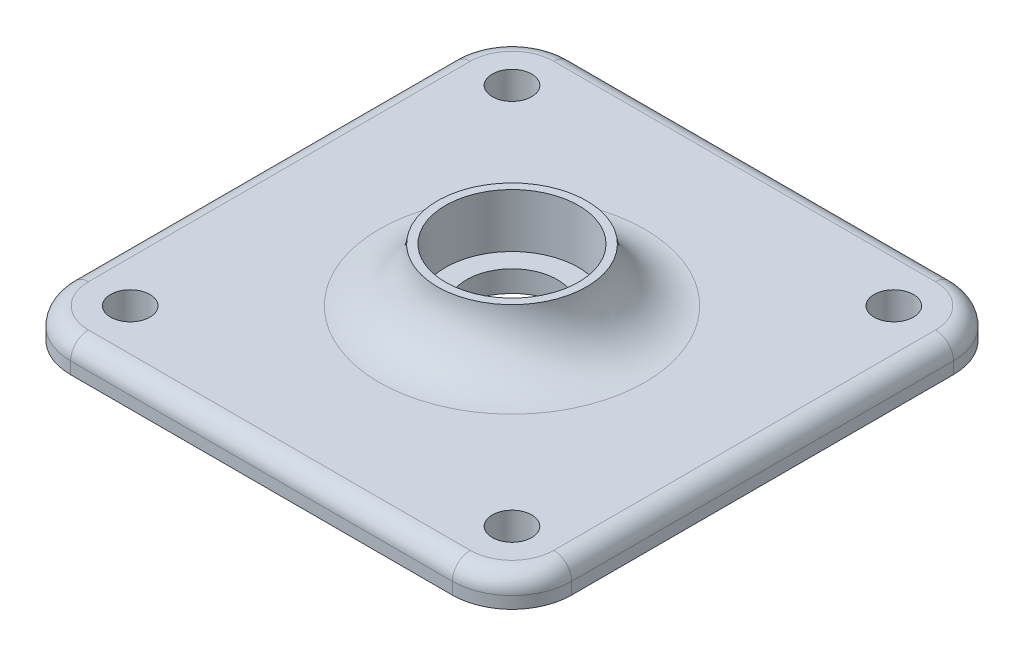
SolidWorks part; units mm, degrees
ref_plane "Front Plane" through (0, 0, 0) normal (0, 0, 1) x (1, 0, 0)
ref_plane "Top Plane" through (0, 0, 0) normal (0, 1, 0) x (1, 0, 0)
ref_plane "Right Plane" through (0, 0, 0) normal (1, 0, 0) x (0, 0, -1)
sketch "Sketch1" plane through (0, 0, 0) normal (0, 1, 0) x (1, 0, 0)
  line L1 (32, 42) -> (-32, 42)
  line L2 (42, 32) -> (42, -32)
  line L3 (32, -42) -> (-32, -42)
  line L4 (-42, 32) -> (-42, -32)
  line L5 (42, 42) -> (-42, -42) construction
  line L6 (42, -42) -> (-42, 42) construction
  arc A0 (32, 42) -> (42, 32) centre (32, 32) cw
  arc A1 (42, -32) -> (32, -42) centre (32, -32) cw
  arc A2 (-32, -42) -> (-42, -32) centre (-32, -32) cw
  arc A3 (-32, 42) -> (-42, 32) centre (-32, 32) ccw
  point P0 (0, 0)
  dimension "D1" = 10
  dimension "D2" = 84
extrude "Boss-Extrude1" add sketch "Sketch1" along normal blind 5 contours L1 A3 L4 A2 L3 A1 L2 A0
sketch "Sketch3" plane through (0, 0, 0) normal (0, 0, 1) x (1, 0, 0)
  line L0 (32, 5) -> (-32, 5) construction
  line L1 (0, 5) -> (-12.5, 5) construction
  line L3 (12.5, 14) -> (-12.5, 14) construction
  line L4 (-12.5, 5) -> (-12.5, 14) construction
  line L5 (-12.5, 5) -> (-11.15, 5)
  line L7 (-12.5, 14) -> (-11.15, 14)
  line L8 (-11.15, 14) -> (-11.15, 5)
  line L9 (-32, 5) -> (-12.5, 5)
  line L10 (0, 0) -> (0, -50000) construction
  line L11 (0, 5) -> (-9.6, 5)
  line L12 (0, 5) -> (0, 0)
  line L13 (-9.6, 5) -> (-9.6, 0)
  line L14 (32, 0) -> (-32, 0) construction
  line L15 (-9.6, 0) -> (0, 0)
  arc A0 (-12.5, 14) -> (-22.25, 5) centre (-22.4501, 14.998) cw
  arc A3 (-9.6, 0) -> (-7.6, 5) centre (-7.3717, 2.0087) cw
  dimension "D4" = 10
  dimension "D8" = 3
  dimension "D1" = 12.5
  dimension "D2" = 9
  dimension "D3" = 11.15
  dimension "D5" = 9.6
  dimension "D9" = 2
revolve "Revolve2" add sketch "Sketch3" angle 360 about L10
revolve "Cut-Revolve2" cut sketch "Sketch3<5>" angle 360 about L10 region at (-4.7402, 2.4691, 0)
sketch "Sketch3<5>" plane through (0, 0, 0) normal (0, 0, 1) x (1, 0, 0) same geometry as "Sketch3"
fillet "Fillet1" radius 3 8 edges at (42, 5, 0) (39.0711, 5, -39.0711) (0, 5, -42) (-39.0711, 5, -39.0711) (-42, 5, 0) (-39.0711, 5, 39.0711) (0, 5, 42) (39.0711, 5, 39.0711)
sketch "Sketch13" plane through (0, 5, 0) normal (0, 1, 0) x (1, 0, 0)
  line L1 (32, 32) -> (-32, 32) construction
  line L2 (32, 32) -> (32, -32) construction
  line L3 (32, -32) -> (-32, -32) construction
  line L4 (-32, 32) -> (-32, -32) construction
  line L5 (32, 32) -> (-32, -32) construction
  line L6 (32, -32) -> (-32, 32) construction
  point P0 (0, 0)
  dimension "D1" = 64
hole_wizard "M6 Clearance Hole1" positions "Sketch16" profile "Sketch18" hole size "M6" standard "ANSI Metric"
sketch "Sketch16" plane through (0, 5, 0) normal (0, 1, 0) x (1, 0, 0)
  point P0 (-32, 32)
  point P3 (-32, -32)
  point P6 (32, -32)
  point P9 (32, 32)
sketch "Sketch18" plane through (-32, 5, -32) normal (1, 0, 0) x (0, 0, 1)
  line L0 (0, 0) -> (0, 9.9828)
  line L1 (0, 9.9828) -> (3.3, 8)
  line L2 (3.3, 8) -> (3.3, 0)
  line L5 (3.3, 0) -> (0, 0)
  line L10 (0, 9.9828) -> (-3.3, 8) construction
  line L11 (0, -6.35) -> (0, 107.95) construction
  dimension "Hole Dia." = 6.6
  dimension "Hole Depth" = 8
  dimension "Drill Angle" = 118
